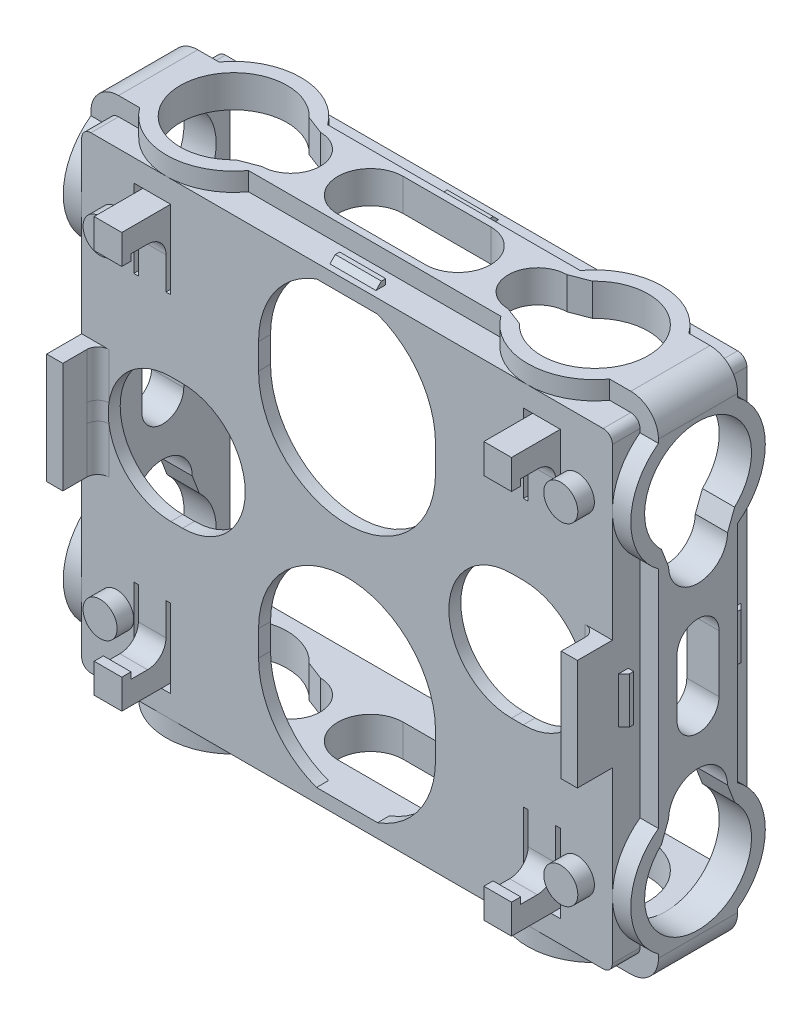
SolidWorks part; units mm, degrees
ref_plane "正面" through (0, 0, 0) normal (0, 0, 1) x (1, 0, 0)
ref_plane "平面" through (0, 0, 0) normal (0, 1, 0) x (1, 0, 0)
ref_plane "右側面" through (0, 0, 0) normal (1, 0, 0) x (0, 0, -1)
sketch "ｽｹｯﾁ2" plane through (0, 0, 0) normal (0, 0, 1) x (1, 0, 0)
  line L0 (0, 0) -> (54, 0) construction
  line L1 (0, 20) -> (54, 20) construction
  line L2 (-3.8, 47.4) -> (57.8, 47.4)
  line L3 (54, 0) -> (54, 40) construction
  line L4 (54, 40) -> (0, 40) construction
  line L5 (0, 40) -> (0, 0) construction
  line L6 (57.8, 47.4) -> (57.8, -7.4)
  line L7 (57.8, -7.4) -> (-3.8, -7.4)
  line L8 (-3.8, -7.4) -> (-3.8, 47.4)
  line L9 (27, 47.4) -> (27, -7.4) construction
  line L10 (27, 32.0981) -> (27, 34.8848) construction
  line L11 (17.3965, 32.0981) -> (17.3965, 34.8848)
  line L12 (36.6035, 32.0981) -> (36.6035, 34.8848)
  line L13 (27, 7.9019) -> (27, 5.1152) construction
  line L14 (17.3965, 7.9019) -> (17.3965, 5.1152)
  line L15 (36.6035, 7.9019) -> (36.6035, 5.1152)
  line L16 (52, 20) -> (27, 20) construction
  line L18 (46.1198, 20) -> (44.8536, 20) construction
  line L19 (52, 23.9649) -> (52, 16.0351) construction
  line L20 (46.1198, 13.1981) -> (44.8536, 13.1981)
  line L21 (46.1198, 26.8019) -> (44.8536, 26.8019)
  line L22 (7.8802, 20) -> (9.1464, 20) construction
  line L23 (7.8802, 13.1981) -> (9.1464, 13.1981)
  line L24 (7.8802, 26.8019) -> (9.1464, 26.8019)
  circle A0 centre (2, 2) radius 1.1 construction
  circle A1 centre (52, 2) radius 1.1 construction
  circle A2 centre (52, 38) radius 1.1 construction
  circle A3 centre (2, 38) radius 1.1 construction
  circle A4 centre (2, 38) radius 1.05
  circle A5 centre (2, 38) radius 1.8491
  circle A6 centre (2, 2) radius 1.8491
  circle A7 centre (52, 2) radius 1.8491
  circle A8 centre (52, 38) radius 1.8491
  circle A9 centre (52, 38) radius 1.05
  circle A10 centre (52, 2) radius 1.05
  circle A11 centre (2, 2) radius 1.05
  arc A12 (17.3965, 32.0981) -> (36.6035, 32.0981) centre (27, 32.0981) ccw
  arc A13 (36.6035, 34.8848) -> (17.3965, 34.8848) centre (27, 34.8848) ccw
  arc A14 (46.1198, 13.1981) -> (46.1198, 26.8019) centre (46.1198, 20) ccw
  arc A15 (44.8536, 26.8019) -> (44.8536, 13.1981) centre (44.8536, 20) ccw
  arc A16 (7.8802, 13.1981) -> (7.8802, 26.8019) centre (7.8802, 20) cw
  arc A17 (9.1464, 26.8019) -> (9.1464, 13.1981) centre (9.1464, 20) cw
  arc A18 (17.3965, 7.9019) -> (36.6035, 7.9019) centre (27, 7.9019) cw
  arc A19 (36.6035, 5.1152) -> (17.3965, 5.1152) centre (27, 5.1152) cw
  point P30 (27, 33.4915)
  point P41 (45.4867, 20)
  point P48 (8.5133, 20)
  point P55 (27, 6.5085)
  dimension "D3" = 2.2
  dimension "D8" = 2.1
  dimension "D9" = 30.8
  dimension "D1" = 40
  dimension "D2" = 54
  dimension "D4" = 27.4
  dimension "D5" = 27.4
extrude "ﾎﾞｽ - 押し出し1" add sketch "ｽｹｯﾁ2" along normal blind 1.5 contours L7 L8 L2 L6 | L15 A19 L14 A18 | L20 A15 L21 A14 | L11 A13 L12 A12 | A17 L23 A16 L24
extrude "ﾎﾞｽ - 押し出し3" add sketch "ｽｹｯﾁ2<4>" along normal blind 3.3 contours A7 | A6 | A5 | A8
sketch "ｽｹｯﾁ2<4>" plane through (0, 0, 0) normal (0, 0, 1) x (1, 0, 0) same geometry as "ｽｹｯﾁ2"
sketch "ｽｹｯﾁ6" plane through (-3.8, 0, 0) normal (-1, 0, 0) x (0, 0, 1)
  line L0 (1.5, -7.4) -> (0, -7.4) construction
  line L7 (1.5, -7.4) -> (1.5, 47.4) construction
  line L8 (-9.6, 33.9866) -> (-8.8, 31.9) construction
  line L9 (-5.8, 43.7) -> (-5.8, 19.9) construction
  line L12 (-13.1, 20) -> (0, 20) construction
  line L14 (-2.8, 31.9) -> (-2, 33.9866) construction
  line L15 (-9.6, 33.9866) -> (-8.8, 31.9) construction
  line L20 (-13.1, 47.4) -> (-13.1, -7.4)
  line L21 (1.5, -7.4) -> (1.5, 47.4)
  line L22 (-5.8, 23.1) -> (-5.8, 16.9) construction
  line L23 (-3.5215, 23.1) -> (-3.5215, 16.9)
  line L24 (-8.0785, 23.1) -> (-8.0785, 16.9)
  line L26 (1.5, 47.4) -> (-13.1, 47.4)
  line L27 (1.5, -7.4) -> (-13.1, -7.4)
  line L28 (-2.8, 31.9) -> (-2, 33.9866) construction
  line L29 (0, -7.4) -> (0, 47.4) construction
  line L30 (-2.8, 8.1) -> (-2, 6.0134) construction
  line L31 (-9.6, 6.0134) -> (-8.8, 8.1) construction
  line L32 (0, 16.9) -> (-11.6, 16.9) construction
  line L33 (-9.7702, 33.8718) -> (-8.9998, 31.8624)
  line L34 (-2.6002, 31.8624) -> (-1.8298, 33.8718)
  line L35 (-2.6002, 8.1376) -> (-1.8298, 6.1282)
  line L36 (-9.7702, 6.1282) -> (-8.9998, 8.1376)
  arc A3 (-2, 33.9866) -> (-9.6, 33.9866) centre (-5.8, 38.1) ccw construction
  arc A4 (-2, 33.9866) -> (-9.6, 33.9866) centre (-5.8, 38.1) ccw construction
  arc A10 (-8.8, 31.9) -> (-2.8, 31.9) centre (-5.8, 31.9) ccw construction
  arc A11 (-8.8, 31.9) -> (-2.8, 31.9) centre (-5.8, 31.9) ccw construction
  arc A12 (-3.5215, 23.1) -> (-8.0785, 23.1) centre (-5.8, 23.1) ccw
  arc A13 (-8.0785, 16.9) -> (-3.5215, 16.9) centre (-5.8, 16.9) ccw
  arc A14 (-8.8, 8.1) -> (-2.8, 8.1) centre (-5.8, 8.1) cw construction
  arc A15 (-2, 6.0134) -> (-9.6, 6.0134) centre (-5.8, 1.9) cw construction
  arc A16 (-1.8298, 33.8718) -> (-9.7702, 33.8718) centre (-5.8, 38.1) ccw
  arc A17 (-8.9998, 31.8624) -> (-2.6002, 31.8624) centre (-5.8, 31.9) ccw
  arc A18 (-8.9998, 8.1376) -> (-2.6002, 8.1376) centre (-5.8, 8.1) cw
  arc A19 (-1.8298, 6.1282) -> (-9.7702, 6.1282) centre (-5.8, 1.9) cw
  point P32 (-5.8, 20)
  dimension "D2" = 0.2
  dimension "D1" = 0
extrude "ﾎﾞｽ - 押し出し4" add sketch "ｽｹｯﾁ6" against normal up to surface (3.5 mm away)
sketch "ｽｹｯﾁ9" plane through (57.8, 0, 0) normal (1, 0, 0) x (0, 0, -1)
  line L2 (8.9998, 31.8624) -> (9.7702, 33.8718)
  line L3 (1.8298, 33.8718) -> (2.6002, 31.8624)
  line L4 (8.9998, 31.8624) -> (9.7702, 33.8718)
  line L5 (1.8298, 33.8718) -> (2.6002, 31.8624)
  line L6 (2.6002, 8.1376) -> (1.8298, 6.1282)
  line L7 (9.7702, 6.1282) -> (8.9998, 8.1376)
  line L8 (2.6002, 8.1376) -> (1.8298, 6.1282)
  line L9 (9.7702, 6.1282) -> (8.9998, 8.1376)
  line L10 (3.5215, 23.1) -> (3.5215, 16.9)
  line L11 (8.0785, 16.9) -> (8.0785, 23.1)
  line L12 (3.5215, 23.1) -> (3.5215, 16.9)
  line L13 (8.0785, 16.9) -> (8.0785, 23.1)
  line L16 (-1.5, 47.4) -> (-1.5, -7.4)
  line L17 (13.1, 47.4) -> (-1.5, 47.4)
  line L18 (13.1, -7.4) -> (13.1, 47.4)
  line L19 (-1.5, -7.4) -> (13.1, -7.4)
  line L20 (-1.5, 47.4) -> (-1.5, -7.4)
  line L21 (13.1, 47.4) -> (-1.5, 47.4)
  line L22 (13.1, -7.4) -> (13.1, 47.4)
  line L23 (-1.5, -7.4) -> (13.1, -7.4)
  arc A2 (2.6002, 31.8624) -> (8.9998, 31.8624) centre (5.8, 31.9) ccw
  arc A3 (9.7702, 33.8718) -> (1.8298, 33.8718) centre (5.8, 38.1) ccw
  arc A4 (2.6002, 31.8624) -> (8.9998, 31.8624) centre (5.8, 31.9) ccw
  arc A5 (9.7702, 33.8718) -> (1.8298, 33.8718) centre (5.8, 38.1) ccw
  arc A6 (1.8298, 6.1282) -> (9.7702, 6.1282) centre (5.8, 1.9) ccw
  arc A7 (8.9998, 8.1376) -> (2.6002, 8.1376) centre (5.8, 8.1) ccw
  arc A8 (1.8298, 6.1282) -> (9.7702, 6.1282) centre (5.8, 1.9) ccw
  arc A9 (8.9998, 8.1376) -> (2.6002, 8.1376) centre (5.8, 8.1) ccw
  arc A10 (3.5215, 16.9) -> (8.0785, 16.9) centre (5.8, 16.9) ccw
  arc A11 (8.0785, 23.1) -> (3.5215, 23.1) centre (5.8, 23.1) ccw
  arc A12 (3.5215, 16.9) -> (8.0785, 16.9) centre (5.8, 16.9) ccw
  arc A13 (8.0785, 23.1) -> (3.5215, 23.1) centre (5.8, 23.1) ccw
  dimension "D1" = 0
  dimension "D2" = 0
  dimension "D3" = 0
  dimension "D4" = 0
extrude "ﾎﾞｽ - 押し出し6" add sketch "ｽｹｯﾁ9" against normal up to surface (3.5 mm away)
sketch "ｽｹｯﾁ10" plane through (0, -7.4, 0) normal (0, -1, 0) x (1, 0, 0)
  line L0 (22.25, -5.8) -> (31.75, -5.8) construction
  line L1 (22.25, -2.25) -> (31.75, -2.25)
  line L2 (22.25, -9.35) -> (31.75, -9.35)
  line L5 (27, 1.5) -> (27, -13.1) construction
  line L10 (16.8, -5.8) -> (37.2, -5.8) construction
  line L11 (21.4, -5.8) -> (32.6, -5.8) construction
  line L13 (21.4, -2.55) -> (32.6, -2.55) construction
  line L14 (21.4, -9.05) -> (32.6, -9.05) construction
  line L17 (11.5134, -9.6) -> (13.6, -8.8)
  line L18 (57.8, 1.5) -> (57.8, -13.1) construction
  line L19 (57.8, 1.5) -> (-3.8, 1.5) construction
  line L20 (-3.8, 1.5) -> (-3.8, -13.1) construction
  line L22 (13.6, -2.8) -> (11.5134, -2)
  line L23 (57.8, 1.5) -> (57.8, -13.1)
  line L24 (57.8, 1.5) -> (-3.8, 1.5)
  line L25 (-3.8, 1.5) -> (-3.8, -13.1)
  line L27 (11.5134, -9.6) -> (13.6, -8.8) construction
  line L28 (13.6, -2.8) -> (11.5134, -2) construction
  line L29 (-3.8, -13.1) -> (57.8, -13.1)
  line L46 (11.6282, -9.7702) -> (13.6376, -8.9998)
  line L47 (13.6376, -2.6002) -> (11.6282, -1.8298)
  line L48 (40.4, -2.8) -> (42.4866, -2) construction
  line L49 (42.4866, -9.6) -> (40.4, -8.8) construction
  line L50 (40.3624, -2.6002) -> (42.3718, -1.8298)
  line L51 (42.3718, -9.7702) -> (40.3624, -8.9998)
  arc A1 (22.25, -2.25) -> (22.25, -9.35) centre (22.25, -5.8) ccw
  arc A2 (31.75, -9.35) -> (31.75, -2.25) centre (31.75, -5.8) ccw
  arc A8 (21.4, -2.55) -> (21.4, -9.05) centre (21.4, -5.8) ccw construction
  arc A9 (32.6, -9.05) -> (32.6, -2.55) centre (32.6, -5.8) ccw construction
  arc A12 (11.5134, -2) -> (11.5134, -9.6) centre (7.4, -5.8) ccw
  arc A13 (13.6, -8.8) -> (13.6, -2.8) centre (13.6, -5.8) ccw
  arc A14 (11.5134, -2) -> (11.5134, -9.6) centre (7.4, -5.8) ccw construction
  arc A15 (13.6, -8.8) -> (13.6, -2.8) centre (13.6, -5.8) ccw construction
  arc A32 (11.6282, -1.8298) -> (11.6282, -9.7702) centre (7.4, -5.8) ccw
  arc A33 (13.6376, -8.9998) -> (13.6376, -2.6002) centre (13.6, -5.8) ccw
  arc A34 (40.4, -8.8) -> (40.4, -2.8) centre (40.4, -5.8) cw construction
  arc A35 (42.4866, -2) -> (42.4866, -9.6) centre (46.6, -5.8) cw construction
  arc A36 (40.3624, -8.9998) -> (40.3624, -2.6002) centre (40.4, -5.8) cw
  arc A37 (42.3718, -1.8298) -> (42.3718, -9.7702) centre (46.6, -5.8) cw
  point P24 (27, -5.8)
  point P41 (27, -5.8)
  dimension "D1" = 0
  dimension "D4" = 11.2
  dimension "D2" = 0.2
  dimension "D3" = 6.5
extrude "ﾎﾞｽ - 押し出し7" add sketch "ｽｹｯﾁ10" against normal blind 3.5
sketch "ｽｹｯﾁ11" plane through (0, 47.4, 0) normal (0, 1, 0) x (1, 0, 0)
  line L2 (40.3624, 2.6002) -> (42.3718, 1.8298)
  line L3 (42.3718, 9.7702) -> (40.3624, 8.9998)
  line L4 (57.8, -1.5) -> (57.8, 13.1)
  line L5 (57.8, 13.1) -> (-3.8, 13.1)
  line L6 (-3.8, 13.1) -> (-3.8, -1.5)
  line L7 (-3.8, -1.5) -> (57.8, -1.5)
  line L8 (57.8, -1.5) -> (57.8, 13.1)
  line L9 (57.8, 13.1) -> (-3.8, 13.1)
  line L10 (-3.8, 13.1) -> (-3.8, -1.5)
  line L11 (-3.8, -1.5) -> (57.8, -1.5)
  line L12 (40.3624, 2.6002) -> (42.3718, 1.8298)
  line L13 (42.3718, 9.7702) -> (40.3624, 8.9998)
  line L14 (13.6376, 8.9998) -> (11.6282, 9.7702)
  line L15 (11.6282, 1.8298) -> (13.6376, 2.6002)
  line L16 (13.6376, 8.9998) -> (11.6282, 9.7702)
  line L17 (11.6282, 1.8298) -> (13.6376, 2.6002)
  line L18 (22.25, 2.25) -> (31.75, 2.25)
  line L19 (31.75, 9.35) -> (22.25, 9.35)
  line L20 (22.25, 2.25) -> (31.75, 2.25)
  line L21 (31.75, 9.35) -> (22.25, 9.35)
  arc A2 (42.3718, 1.8298) -> (42.3718, 9.7702) centre (46.6, 5.8) ccw
  arc A3 (40.3624, 8.9998) -> (40.3624, 2.6002) centre (40.4, 5.8) ccw
  arc A4 (42.3718, 1.8298) -> (42.3718, 9.7702) centre (46.6, 5.8) ccw
  arc A5 (40.3624, 8.9998) -> (40.3624, 2.6002) centre (40.4, 5.8) ccw
  arc A6 (13.6376, 2.6002) -> (13.6376, 8.9998) centre (13.6, 5.8) ccw
  arc A7 (11.6282, 9.7702) -> (11.6282, 1.8298) centre (7.4, 5.8) ccw
  arc A8 (13.6376, 2.6002) -> (13.6376, 8.9998) centre (13.6, 5.8) ccw
  arc A9 (11.6282, 9.7702) -> (11.6282, 1.8298) centre (7.4, 5.8) ccw
  arc A10 (31.75, 2.25) -> (31.75, 9.35) centre (31.75, 5.8) ccw
  arc A11 (22.25, 9.35) -> (22.25, 2.25) centre (22.25, 5.8) ccw
  arc A12 (31.75, 2.25) -> (31.75, 9.35) centre (31.75, 5.8) ccw
  arc A13 (22.25, 9.35) -> (22.25, 2.25) centre (22.25, 5.8) ccw
  dimension "D1" = 0
  dimension "D2" = 0
  dimension "D3" = 0
  dimension "D4" = 0
extrude "ﾎﾞｽ - 押し出し8" add sketch "ｽｹｯﾁ11" against normal blind 3.5
fillet "ﾌｨﾚｯﾄ1" radius 3 4 edges at (-3.8, -7.4, -5.8) (57.8, -7.4, -5.8) (57.8, 47.4, -5.8) (-3.8, 47.4, -5.8)
sketch "ｽｹｯﾁ12" plane through (0, 0, -13.1) normal (0, 0, -1) x (-1, 0, 0)
  line L1 (-55.8, 44.4) -> (-55.8, -4.4)
  line L2 (-54.8, -5.4) -> (0.8, -5.4)
  line L3 (1.8, -4.4) -> (1.8, 44.4)
  line L4 (-54.8, -7.4) -> (0.8, -7.4)
  line L5 (3.8, -4.4) -> (3.8, 44.4)
  line L6 (-54.8, -7.4) -> (0.8, -7.4)
  line L7 (-57.8, 44.4) -> (-57.8, -4.4)
  line L8 (0.8, 47.4) -> (-54.8, 47.4)
  line L9 (3.8, -4.4) -> (3.8, 44.4)
  line L10 (0.8, 47.4) -> (-54.8, 47.4)
  line L11 (-57.8, 44.4) -> (-57.8, -4.4)
  line L12 (0.8, 45.4) -> (-54.8, 45.4)
  line L16 (-57.8, 44.4) -> (-57.8, -4.4) construction
  line L17 (-54.8, -7.4) -> (0.8, -7.4) construction
  line L18 (0.8, 47.4) -> (-54.8, 47.4) construction
  arc A0 (-54.8, 45.4) -> (-55.8, 44.4) centre (-54.8, 44.4) ccw
  arc A1 (-55.8, -4.4) -> (-54.8, -5.4) centre (-54.8, -4.4) ccw
  arc A2 (0.8, -5.4) -> (1.8, -4.4) centre (0.8, -4.4) ccw
  arc A3 (1.8, 44.4) -> (0.8, 45.4) centre (0.8, 44.4) ccw
  arc A4 (0.8, -7.4) -> (3.8, -4.4) centre (0.8, -4.4) ccw
  arc A5 (3.8, 44.4) -> (0.8, 47.4) centre (0.8, 44.4) ccw
  arc A6 (-54.8, 47.4) -> (-57.8, 44.4) centre (-54.8, 44.4) ccw
  arc A7 (-57.8, -4.4) -> (-54.8, -7.4) centre (-54.8, -4.4) ccw
  arc A8 (0.8, -7.4) -> (3.8, -4.4) centre (0.8, -4.4) ccw
  arc A9 (3.8, 44.4) -> (0.8, 47.4) centre (0.8, 44.4) ccw
  arc A10 (-54.8, 47.4) -> (-57.8, 44.4) centre (-54.8, 44.4) ccw
  arc A11 (-57.8, -4.4) -> (-54.8, -7.4) centre (-54.8, -4.4) ccw
  dimension "D1" = 0
  dimension "D2" = 2
extrude "ｶｯﾄ - 押し出し1" cut sketch "ｽｹｯﾁ12" against normal blind 3
sketch "ｽｹｯﾁ22" plane through (0, 0, 1.5) normal (0, 0, 1) x (1, 0, 0)
  line L0 (-1.8, 44.4) -> (-1.8, -4.4)
  line L1 (-0.8, -5.4) -> (54.8, -5.4)
  line L2 (55.8, -4.4) -> (55.8, 44.4)
  line L3 (54.8, 45.4) -> (-0.8, 45.4)
  line L4 (-3.8, 44.4) -> (-3.8, -4.4)
  line L5 (-0.8, -7.4) -> (54.8, -7.4)
  line L6 (57.8, -4.4) -> (57.8, 44.4)
  line L7 (54.8, 47.4) -> (-0.8, 47.4)
  line L8 (-3.8, 44.4) -> (-3.8, -4.4)
  line L9 (-0.8, -7.4) -> (54.8, -7.4)
  line L10 (57.8, -4.4) -> (57.8, 44.4)
  line L11 (54.8, 47.4) -> (-0.8, 47.4)
  arc A0 (-1.8, -4.4) -> (-0.8, -5.4) centre (-0.8, -4.4) ccw
  arc A1 (54.8, -5.4) -> (55.8, -4.4) centre (54.8, -4.4) ccw
  arc A2 (55.8, 44.4) -> (54.8, 45.4) centre (54.8, 44.4) ccw
  arc A3 (-0.8, 45.4) -> (-1.8, 44.4) centre (-0.8, 44.4) ccw
  arc A4 (-3.8, -4.4) -> (-0.8, -7.4) centre (-0.8, -4.4) ccw
  arc A5 (54.8, -7.4) -> (57.8, -4.4) centre (54.8, -4.4) ccw
  arc A6 (57.8, 44.4) -> (54.8, 47.4) centre (54.8, 44.4) ccw
  arc A7 (-0.8, 47.4) -> (-3.8, 44.4) centre (-0.8, 44.4) ccw
  arc A8 (-3.8, -4.4) -> (-0.8, -7.4) centre (-0.8, -4.4) ccw
  arc A9 (54.8, -7.4) -> (57.8, -4.4) centre (54.8, -4.4) ccw
  arc A10 (57.8, 44.4) -> (54.8, 47.4) centre (54.8, 44.4) ccw
  arc A11 (-0.8, 47.4) -> (-3.8, 44.4) centre (-0.8, 44.4) ccw
  dimension "D1" = 0
  dimension "D2" = 2
extrude "ｶｯﾄ - 押し出し2" cut sketch "ｽｹｯﾁ22" against normal blind 3
sketch "ｽｹｯﾁ21" plane through (0, -7.4, 0) normal (0, -1, 0) x (1, 0, 0)
  line L0 (-0.8, -5.8) -> (-7.911, -5.8) construction
  line L1 (11.2923, -1.5) -> (42.7077, -1.5) construction
  line L5 (1.5008, -10.1) -> (3.5077, -10.1)
  line L6 (-0.8, -1.5) -> (3.5077, -1.5) construction
  line L10 (11.2923, -1.5) -> (13.2992, -1.5)
  line L11 (-0.8, -1.5) -> (-0.8, -10.1) construction
  line L12 (1.5008, -1.5) -> (3.5077, -1.5)
  line L19 (11.2923, -10.1) -> (13.2992, -10.1)
  line L23 (27, 1.5) -> (27, 9.2892) construction
  line L24 (-0.8, 1.5) -> (54.8, 1.5) construction
  line L25 (42.7077, -10.1) -> (40.7008, -10.1)
  line L26 (52.4992, -1.5) -> (50.4923, -1.5)
  line L27 (42.7077, -1.5) -> (40.7008, -1.5)
  line L28 (52.4992, -10.1) -> (50.4923, -10.1)
  arc A6 (13.2992, -10.1) -> (1.5008, -10.1) centre (7.4, -5.8) cw
  arc A10 (11.2923, -1.5) -> (3.5077, -1.5) centre (7.4, -5.8) ccw construction
  arc A13 (11.2923, -1.5) -> (3.5077, -1.5) centre (7.4, -5.8) ccw
  arc A14 (13.2992, -1.5) -> (1.5008, -1.5) centre (7.4, -5.8) ccw
  arc A25 (12.2989, -0.3879) -> (2.5011, -0.3879) centre (7.4, -5.8) ccw construction
  arc A26 (11.2923, -10.1) -> (3.5077, -10.1) centre (7.4, -5.8) cw
  arc A27 (42.7077, -10.1) -> (50.4923, -10.1) centre (46.6, -5.8) ccw
  arc A28 (40.7008, -1.5) -> (52.4992, -1.5) centre (46.6, -5.8) cw
  arc A29 (42.7077, -1.5) -> (50.4923, -1.5) centre (46.6, -5.8) cw
  arc A30 (40.7008, -10.1) -> (52.4992, -10.1) centre (46.6, -5.8) ccw
  dimension "D1" = 1.5
extrude "ﾎﾞｽ - 押し出し9" add sketch "ｽｹｯﾁ21" against normal up to surface (2 mm away) up to face at (27, -5.4, -0.375)
sketch "ｽｹｯﾁ23" plane through (0, 47.4, 0) normal (0, 1, 0) x (1, 0, 0)
  line L2 (1.5008, 10.1) -> (3.5077, 10.1)
  line L3 (11.2923, 10.1) -> (13.2992, 10.1)
  line L4 (1.5008, 10.1) -> (3.5077, 10.1)
  line L5 (11.2923, 10.1) -> (13.2992, 10.1)
  line L6 (52.4992, 1.5) -> (50.4923, 1.5)
  line L7 (42.7077, 1.5) -> (40.7008, 1.5)
  line L8 (52.4992, 1.5) -> (50.4923, 1.5)
  line L9 (42.7077, 1.5) -> (40.7008, 1.5)
  line L10 (40.7008, 10.1) -> (42.7077, 10.1)
  line L11 (50.4923, 10.1) -> (52.4992, 10.1)
  line L12 (40.7008, 10.1) -> (42.7077, 10.1)
  line L13 (50.4923, 10.1) -> (52.4992, 10.1)
  line L14 (13.2992, 1.5) -> (11.2923, 1.5)
  line L15 (3.5077, 1.5) -> (1.5008, 1.5)
  line L16 (13.2992, 1.5) -> (11.2923, 1.5)
  line L17 (3.5077, 1.5) -> (1.5008, 1.5)
  arc A2 (11.2923, 10.1) -> (3.5077, 10.1) centre (7.4, 5.8) ccw
  arc A3 (13.2992, 10.1) -> (1.5008, 10.1) centre (7.4, 5.8) ccw
  arc A4 (11.2923, 10.1) -> (3.5077, 10.1) centre (7.4, 5.8) ccw
  arc A5 (13.2992, 10.1) -> (1.5008, 10.1) centre (7.4, 5.8) ccw
  arc A6 (42.7077, 1.5) -> (50.4923, 1.5) centre (46.6, 5.8) ccw
  arc A7 (40.7008, 1.5) -> (52.4992, 1.5) centre (46.6, 5.8) ccw
  arc A8 (42.7077, 1.5) -> (50.4923, 1.5) centre (46.6, 5.8) ccw
  arc A9 (40.7008, 1.5) -> (52.4992, 1.5) centre (46.6, 5.8) ccw
  arc A10 (52.4992, 10.1) -> (40.7008, 10.1) centre (46.6, 5.8) ccw
  arc A11 (50.4923, 10.1) -> (42.7077, 10.1) centre (46.6, 5.8) ccw
  arc A12 (52.4992, 10.1) -> (40.7008, 10.1) centre (46.6, 5.8) ccw
  arc A13 (50.4923, 10.1) -> (42.7077, 10.1) centre (46.6, 5.8) ccw
  arc A14 (1.5008, 1.5) -> (13.2992, 1.5) centre (7.4, 5.8) ccw
  arc A15 (3.5077, 1.5) -> (11.2923, 1.5) centre (7.4, 5.8) ccw
  arc A16 (1.5008, 1.5) -> (13.2992, 1.5) centre (7.4, 5.8) ccw
  arc A17 (3.5077, 1.5) -> (11.2923, 1.5) centre (7.4, 5.8) ccw
  dimension "D1" = 0
  dimension "D2" = 0
  dimension "D3" = 0
  dimension "D4" = 0
extrude "ﾎﾞｽ - 押し出し10" add sketch "ｽｹｯﾁ23" against normal up to surface (2 mm away) up to face at (27, 45.4, -11.225)
sketch "ｽｹｯﾁ24" plane through (57.8, 0, 0) normal (1, 0, 0) x (0, 0, -1)
  line L0 (1.5, 5.7923) -> (1.5, 34.2077) construction
  line L1 (1.5, 41.9923) -> (1.5, 44.4) construction
  line L3 (1.5, 41.9923) -> (1.5, 43.9992)
  line L4 (1.5, 32.2008) -> (1.5, 34.2077)
  line L7 (5.8, 44.4) -> (5.8, 52.6929) construction
  line L8 (10.1, 44.4) -> (1.5, 44.4) construction
  line L9 (10.1, 32.2008) -> (10.1, 34.2077)
  line L10 (10.1, 41.9923) -> (10.1, 43.9992)
  line L11 (-1.5, 20) -> (-9.7166, 20) construction
  line L15 (-1.5, -4.4) -> (-1.5, 44.4) construction
  line L22 (10.1, -1.9923) -> (10.1, -3.9992)
  line L23 (10.1, 7.7992) -> (10.1, 5.7923)
  line L24 (1.5, 7.7992) -> (1.5, 5.7923)
  line L25 (1.5, -1.9923) -> (1.5, -3.9992)
  arc A0 (1.5, 43.9992) -> (1.5, 32.2008) centre (5.8, 38.1) ccw
  arc A1 (0.3879, 42.9989) -> (0.3879, 33.2011) centre (5.8, 38.1) ccw construction
  arc A7 (1.5, 41.9923) -> (1.5, 34.2077) centre (5.8, 38.1) ccw construction
  arc A11 (1.5, 41.9923) -> (1.5, 34.2077) centre (5.8, 38.1) ccw
  arc A12 (10.1, 43.9992) -> (10.1, 32.2008) centre (5.8, 38.1) cw
  arc A13 (10.1, -3.9992) -> (10.1, 7.7992) centre (5.8, 1.9) ccw
  arc A14 (1.5, -1.9923) -> (1.5, 5.7923) centre (5.8, 1.9) cw
  arc A15 (1.5, -3.9992) -> (1.5, 7.7992) centre (5.8, 1.9) cw
  arc A16 (10.1, 34.2077) -> (10.1, 41.9923) centre (5.8, 38.1) ccw construction
  arc A17 (10.1, -1.9923) -> (10.1, 5.7923) centre (5.8, 1.9) ccw construction
  arc A18 (10.1, 34.2077) -> (10.1, 41.9923) centre (5.8, 38.1) ccw
  arc A19 (10.1, -1.9923) -> (10.1, 5.7923) centre (5.8, 1.9) ccw
  dimension "D1" = 1.5
extrude "ﾎﾞｽ - 押し出し11" add sketch "ｽｹｯﾁ24" against normal up to surface (2 mm away) up to face at (55.8, 20, -0.375)
sketch "ｽｹｯﾁ25" plane through (-3.8, 0, 0) normal (-1, 0, 0) x (0, 0, 1)
  line L2 (-1.5, 43.9992) -> (-1.5, 41.9923)
  line L3 (-1.5, 34.2077) -> (-1.5, 32.2008)
  line L4 (-1.5, 43.9992) -> (-1.5, 41.9923)
  line L5 (-1.5, 34.2077) -> (-1.5, 32.2008)
  line L6 (-1.5, 7.7992) -> (-1.5, 5.7923)
  line L7 (-1.5, -1.9923) -> (-1.5, -3.9992)
  line L8 (-1.5, 7.7992) -> (-1.5, 5.7923)
  line L9 (-1.5, -1.9923) -> (-1.5, -3.9992)
  line L10 (-10.1, -3.9992) -> (-10.1, -1.9923)
  line L11 (-10.1, 5.7923) -> (-10.1, 7.7992)
  line L12 (-10.1, -3.9992) -> (-10.1, -1.9923)
  line L13 (-10.1, 5.7923) -> (-10.1, 7.7992)
  line L14 (-10.1, 32.2008) -> (-10.1, 34.2077)
  line L15 (-10.1, 41.9923) -> (-10.1, 43.9992)
  line L16 (-10.1, 32.2008) -> (-10.1, 34.2077)
  line L17 (-10.1, 41.9923) -> (-10.1, 43.9992)
  arc A2 (-1.5, 32.2008) -> (-1.5, 43.9992) centre (-5.8, 38.1) ccw
  arc A3 (-1.5, 34.2077) -> (-1.5, 41.9923) centre (-5.8, 38.1) ccw
  arc A4 (-1.5, 32.2008) -> (-1.5, 43.9992) centre (-5.8, 38.1) ccw
  arc A5 (-1.5, 34.2077) -> (-1.5, 41.9923) centre (-5.8, 38.1) ccw
  arc A6 (-1.5, -1.9923) -> (-1.5, 5.7923) centre (-5.8, 1.9) ccw
  arc A7 (-1.5, -3.9992) -> (-1.5, 7.7992) centre (-5.8, 1.9) ccw
  arc A8 (-1.5, -1.9923) -> (-1.5, 5.7923) centre (-5.8, 1.9) ccw
  arc A9 (-1.5, -3.9992) -> (-1.5, 7.7992) centre (-5.8, 1.9) ccw
  arc A10 (-10.1, 7.7992) -> (-10.1, -3.9992) centre (-5.8, 1.9) ccw
  arc A11 (-10.1, 5.7923) -> (-10.1, -1.9923) centre (-5.8, 1.9) ccw
  arc A12 (-10.1, 7.7992) -> (-10.1, -3.9992) centre (-5.8, 1.9) ccw
  arc A13 (-10.1, 5.7923) -> (-10.1, -1.9923) centre (-5.8, 1.9) ccw
  arc A14 (-10.1, 43.9992) -> (-10.1, 32.2008) centre (-5.8, 38.1) ccw
  arc A15 (-10.1, 41.9923) -> (-10.1, 34.2077) centre (-5.8, 38.1) ccw
  arc A16 (-10.1, 43.9992) -> (-10.1, 32.2008) centre (-5.8, 38.1) ccw
  arc A17 (-10.1, 41.9923) -> (-10.1, 34.2077) centre (-5.8, 38.1) ccw
  dimension "D1" = 0
  dimension "D2" = 0
  dimension "D3" = 0
  dimension "D4" = 0
extrude "ﾎﾞｽ - 押し出し12" add sketch "ｽｹｯﾁ25" against normal up to surface (2 mm away) up to face at (-1.8, 20, -11.225)
ref_plane "平面1" through (0, 20, 0) normal (0, 1, 0) x (1, 0, 0)
sketch "ｽｹｯﾁ26" plane through (0, 20, 0) normal (0, 1, 0) x (1, 0, 0)
  line L1 (-1.8, 13.1) -> (55.8, 13.1) construction
  line L2 (56.3887, -0.2466) -> (56.3887, 0.2234)
  line L3 (55.8, -0.8353) -> (56.3887, -0.2466)
  line L4 (55.8, 0.2234) -> (55.8, -0.8353)
  line L5 (27, 13.1) -> (27, 21.7666) construction
  line L6 (55.8, 0.2234) -> (56.3887, 0.2234)
  line L7 (57.8, 5.8) -> (54.8, 5.8) construction
  line L8 (57.8, 10.1) -> (57.8, 1.5) construction
  line L9 (54.8, 1.5) -> (54.8, 10.1) construction
  line L10 (55.8, 11.3766) -> (56.3887, 11.3766)
  line L11 (55.8, 11.3766) -> (55.8, 12.4353)
  line L12 (55.8, 12.4353) -> (56.3887, 11.8466)
  line L13 (56.3887, 11.8466) -> (56.3887, 11.3766)
  line L14 (-2.3887, 11.8466) -> (-2.3887, 11.3766)
  line L15 (-1.8, 12.4353) -> (-2.3887, 11.8466)
  line L16 (-1.8, 11.3766) -> (-1.8, 12.4353)
  line L17 (-1.8, 11.3766) -> (-2.3887, 11.3766)
  line L18 (-1.8, 0.2234) -> (-2.3887, 0.2234)
  line L19 (-1.8, 0.2234) -> (-1.8, -0.8353)
  line L20 (-1.8, -0.8353) -> (-2.3887, -0.2466)
  line L21 (-2.3887, -0.2466) -> (-2.3887, 0.2234)
extrude "ﾎﾞｽ - 押し出し13" add sketch "ｽｹｯﾁ26" along normal mid plane 5
ref_plane "平面3" through (27, 0, 0) normal (-1, 0, 0) x (0, 0, 1)
sketch "ｽｹｯﾁ27" plane through (27, 0, 0) normal (-1, 0, 0) x (0, 0, 1)
  line L0 (0.2713, 45.9887) -> (-0.1987, 45.9887)
  line L1 (0.86, 45.4) -> (0.2713, 45.9887)
  line L2 (-0.1987, 45.4) -> (0.86, 45.4)
  line L3 (-1.5, -5.4) -> (1.5, -5.4) construction
  line L4 (-5.8, 47.4) -> (-5.8, 44.4) construction
  line L5 (-1.5, 45.4) -> (1.5, 45.4) construction
  line L6 (-1.5, -5.4) -> (1.5, -5.4) construction
  line L7 (1.5, 45.4) -> (1.5, -5.4) construction
  line L8 (1.5, 20) -> (10.2973, 20) construction
  line L9 (-0.1987, 45.9887) -> (-0.1987, 45.4)
  line L10 (-1.5, 47.4) -> (-10.1, 47.4) construction
  line L11 (-10.1, 44.4) -> (-1.5, 44.4) construction
  line L12 (-11.4013, 45.4) -> (-12.46, 45.4)
  line L13 (-12.46, 45.4) -> (-11.8713, 45.9887)
  line L14 (-11.8713, 45.9887) -> (-11.4013, 45.9887)
  line L15 (-11.4013, 45.4) -> (-11.4013, 45.9887)
  line L16 (-11.4013, -5.4) -> (-11.4013, -5.9887)
  line L17 (-11.8713, -5.9887) -> (-11.4013, -5.9887)
  line L18 (-12.46, -5.4) -> (-11.8713, -5.9887)
  line L19 (-11.4013, -5.4) -> (-12.46, -5.4)
  line L20 (-0.1987, -5.9887) -> (-0.1987, -5.4)
  line L21 (-0.1987, -5.4) -> (0.86, -5.4)
  line L22 (0.86, -5.4) -> (0.2713, -5.9887)
  line L23 (0.2713, -5.9887) -> (-0.1987, -5.9887)
extrude "ﾎﾞｽ - 押し出し14" add sketch "ｽｹｯﾁ27" along normal mid plane 5
ref_plane "平面4" through (0, 0, 2.9) normal (0, 0, 1) x (1, 0, 0)
sketch "ｽｹｯﾁ28" plane through (0, 0, 1.5) normal (0, 0, 1) x (1, 0, 0)
  line L0 (0, 0) -> (54, 0) construction
  line L1 (27, 20) -> (-13.2669, 20) construction
  line L2 (-0.05, 14) -> (-1.8, 14)
  line L3 (54, 0) -> (54, 40) construction
  line L4 (54, 40) -> (0, 40) construction
  line L5 (0, 40) -> (0, 0) construction
  line L6 (-1.8, 38.1) -> (-1.8, 1.9) construction
  line L7 (-1.8, 14) -> (-1.8, 26)
  line L8 (-0.05, 26) -> (-0.05, 14)
  line L9 (27, 47.4) -> (27, -7.4) construction
  line L10 (55.8, 26) -> (54.05, 26)
  line L11 (54.05, 26) -> (54.05, 14)
  line L12 (55.8, 14) -> (55.8, 26)
  line L13 (54.05, 14) -> (55.8, 14)
  line L14 (4.35, 42.5) -> (4.35, 40)
  line L15 (4.35, 42.5) -> (7.35, 42.5)
  line L16 (7.35, 42.5) -> (7.35, 40)
  line L17 (4.35, 40) -> (7.35, 40)
  line L18 (4.35, 0) -> (7.35, 0)
  line L19 (7.35, -2.5) -> (7.35, 0)
  line L20 (4.35, -2.5) -> (7.35, -2.5)
  line L21 (4.35, -2.5) -> (4.35, 0)
  line L22 (49.65, -2.5) -> (49.65, 0)
  line L23 (49.65, -2.5) -> (46.65, -2.5)
  line L24 (46.65, -2.5) -> (46.65, 0)
  line L25 (49.65, 0) -> (46.65, 0)
  line L26 (49.65, 40) -> (46.65, 40)
  line L27 (46.65, 42.5) -> (46.65, 40)
  line L28 (49.65, 42.5) -> (46.65, 42.5)
  line L29 (49.65, 42.5) -> (49.65, 40)
  line L30 (-1.8, 26) -> (-0.05, 26)
  circle A21 centre (2, 38) radius 1.8491
  circle A22 centre (2, 38) radius 1.8491 construction
  dimension "D7" = 3
  dimension "D2" = 0.1
  dimension "D6" = 2.35
  dimension "D8" = 2.5
  dimension "D1" = 0
extrude "ﾎﾞｽ - 押し出し15" add sketch "ｽｹｯﾁ28" along normal blind 3.8
sketch "ｽｹｯﾁ29" plane through (0, 0, 5.3) normal (0, 0, 1) x (1, 0, 0)
  line L0 (4.35, 39.3) -> (7.35, 39.3)
  line L1 (7.35, 42.5) -> (7.35, 39.3)
  line L2 (4.35, 42.5) -> (4.35, 39.3)
  line L3 (7.35, 42.5) -> (4.35, 42.5) construction
  line L4 (7.35, 42.5) -> (4.35, 42.5)
  line L5 (-3.8, 20) -> (-15.3419, 20) construction
  line L6 (-3.8, 32.2008) -> (-3.8, 7.7992) construction
  line L7 (7.35, -2.5) -> (4.35, -2.5)
  line L8 (4.35, -2.5) -> (4.35, 0.7)
  line L9 (7.35, -2.5) -> (7.35, 0.7)
  line L11 (4.35, 0.7) -> (7.35, 0.7)
  line L12 (27, 45.4) -> (27, 55.9669) construction
  line L13 (46.6, 45.4) -> (7.4, 45.4) construction
  line L14 (49.65, 0.7) -> (46.65, 0.7)
  line L16 (46.65, -2.5) -> (46.65, 0.7)
  line L17 (49.65, -2.5) -> (49.65, 0.7)
  line L18 (46.65, -2.5) -> (49.65, -2.5)
  line L19 (46.65, 42.5) -> (49.65, 42.5)
  line L20 (49.65, 42.5) -> (49.65, 39.3)
  line L21 (46.65, 42.5) -> (46.65, 39.3)
  line L22 (49.65, 39.3) -> (46.65, 39.3)
extrude "ﾎﾞｽ - 押し出し16" add sketch "ｽｹｯﾁ29" along normal blind 1
sketch "ｽｹｯﾁ30" plane through (0, 0, 1.5) normal (0, 0, 1) x (1, 0, 0)
  line L0 (4.35, 42.5) -> (4.35, 34.5)
  line L1 (7.35, 42.5) -> (7.35, 34.5)
  line L2 (7.85, 43) -> (7.85, 34.5)
  line L3 (7.85, 43) -> (3.85, 43)
  line L4 (7.35, 42.5) -> (4.35, 42.5)
  line L5 (4.35, 42.5) -> (4.35, 39.3)
  line L6 (4.35, 39.3) -> (7.35, 39.3)
  line L7 (7.35, 39.3) -> (7.35, 42.5)
  line L8 (7.35, 42.5) -> (4.35, 42.5)
  line L9 (3.85, 43) -> (3.85, 34.5)
  line L10 (3.85, 34.5) -> (4.35, 34.5)
  line L11 (7.35, 34.5) -> (7.85, 34.5)
  line L12 (-3.8, 20) -> (-12.0524, 20) construction
  line L14 (-3.8, 32.2008) -> (-3.8, 7.7992) construction
  line L15 (7.35, 5.5) -> (7.85, 5.5)
  line L16 (3.85, 5.5) -> (4.35, 5.5)
  line L17 (3.85, -3) -> (3.85, 5.5)
  line L18 (7.35, -2.5) -> (4.35, -2.5)
  line L19 (7.85, -3) -> (3.85, -3)
  line L20 (7.85, -3) -> (7.85, 5.5)
  line L21 (7.35, -2.5) -> (7.35, 5.5)
  line L22 (4.35, -2.5) -> (4.35, 5.5)
  line L24 (27, 47.4) -> (27, 61.077) construction
  line L25 (40.7008, 47.4) -> (13.2992, 47.4) construction
  line L26 (49.65, -2.5) -> (49.65, 5.5)
  line L27 (46.65, -2.5) -> (46.65, 5.5)
  line L28 (46.15, -3) -> (46.15, 5.5)
  line L29 (46.15, -3) -> (50.15, -3)
  line L30 (46.65, -2.5) -> (49.65, -2.5)
  line L31 (50.15, -3) -> (50.15, 5.5)
  line L32 (50.15, 5.5) -> (49.65, 5.5)
  line L33 (46.65, 5.5) -> (46.15, 5.5)
  line L34 (46.65, 34.5) -> (46.15, 34.5)
  line L35 (50.15, 34.5) -> (49.65, 34.5)
  line L36 (50.15, 43) -> (50.15, 34.5)
  line L37 (46.65, 42.5) -> (49.65, 42.5)
  line L38 (46.15, 43) -> (50.15, 43)
  line L39 (46.15, 43) -> (46.15, 34.5)
  line L40 (46.65, 42.5) -> (46.65, 34.5)
  line L41 (49.65, 42.5) -> (49.65, 34.5)
  dimension "D2" = 8
  dimension "D3" = 0.5
  dimension "D1" = 0
extrude "ｶｯﾄ - 押し出し4" cut sketch "ｽｹｯﾁ30" against normal up to vertex up to point (3.55, -3.9, 0)
sketch "ｽｹｯﾁ31" plane through (0, 0, 0) normal (0, 0, -1) x (-1, 0, 0)
  line L4 (0.3, -3.9) -> (0.3, 1.9)
  line L5 (0.3, 43.9) -> (-7.4, 43.9)
  line L6 (-54.3, 1.9) -> (-54.3, -3.9)
  line L7 (-54.3, -3.9) -> (-46.6, -3.9)
  line L8 (0.3, -3.9) -> (0.3, 1.9)
  line L9 (0.3, 43.9) -> (-7.4, 43.9)
  line L10 (-54.3, 1.9) -> (-54.3, -3.9)
  line L11 (-54.3, -3.9) -> (-46.6, -3.9)
  line L18 (-17.3965, 34.8848) -> (-17.3965, 32.0981)
  line L19 (-17.3965, 34.8848) -> (-17.3965, 32.0981)
  line L20 (-36.6035, 32.0981) -> (-36.6035, 34.8848)
  line L21 (-36.6035, 32.0981) -> (-36.6035, 34.8848)
  line L22 (-7.4, 43.9) -> (-23.6902, 43.9)
  line L23 (-7.4, 43.9) -> (-23.6902, 43.9)
  line L24 (-36.6035, 5.1152) -> (-36.6035, 7.9019)
  line L25 (-36.6035, 5.1152) -> (-36.6035, 7.9019)
  line L26 (-17.3965, 7.9019) -> (-17.3965, 5.1152)
  line L27 (-17.3965, 7.9019) -> (-17.3965, 5.1152)
  line L28 (-7.4, -3.9) -> (0.3, -3.9)
  line L29 (-7.4, -3.9) -> (0.3, -3.9)
  line L32 (0.3, 38.1) -> (0.3, 43.9)
  line L33 (0.3, 38.1) -> (0.3, 43.9)
  line L34 (0.3, 1.9) -> (0.3, 38.1)
  line L35 (0.3, 1.9) -> (0.3, 38.1)
  line L38 (-54.3, 38.1) -> (-54.3, 1.9)
  line L39 (-54.3, 38.1) -> (-54.3, 1.9)
  line L40 (-30.3098, 43.9) -> (-46.6, 43.9)
  line L41 (-30.3098, 43.9) -> (-46.6, 43.9)
  line L43 (-23.6902, -3.9) -> (-7.4, -3.9)
  line L44 (-23.6902, -3.9) -> (-7.4, -3.9)
  line L46 (-46.6, -3.9) -> (-30.3098, -3.9)
  line L47 (-46.6, -3.9) -> (-30.3098, -3.9)
  line L50 (-46.6, 43.9) -> (-54.3, 43.9)
  line L51 (-46.6, 43.9) -> (-54.3, 43.9)
  line L52 (-54.3, 43.9) -> (-54.3, 38.1)
  line L53 (-54.3, 43.9) -> (-54.3, 38.1)
  arc A6 (-17.3965, 34.8848) -> (-23.6902, 43.9) centre (-27, 34.8848) ccw
  arc A7 (-17.3965, 34.8848) -> (-23.6902, 43.9) centre (-27, 34.8848) ccw
  arc A8 (-36.6035, 32.0981) -> (-17.3965, 32.0981) centre (-27, 32.0981) ccw
  arc A9 (-36.6035, 32.0981) -> (-17.3965, 32.0981) centre (-27, 32.0981) ccw
  arc A10 (-30.3098, 43.9) -> (-36.6035, 34.8848) centre (-27, 34.8848) ccw
  arc A11 (-30.3098, 43.9) -> (-36.6035, 34.8848) centre (-27, 34.8848) ccw
  arc A12 (-36.6035, 5.1152) -> (-30.3098, -3.9) centre (-27, 5.1152) ccw
  arc A13 (-36.6035, 5.1152) -> (-30.3098, -3.9) centre (-27, 5.1152) ccw
  arc A14 (-17.3965, 7.9019) -> (-36.6035, 7.9019) centre (-27, 7.9019) ccw
  arc A15 (-17.3965, 7.9019) -> (-36.6035, 7.9019) centre (-27, 7.9019) ccw
  arc A16 (-23.6902, -3.9) -> (-17.3965, 5.1152) centre (-27, 5.1152) ccw
  arc A17 (-23.6902, -3.9) -> (-17.3965, 5.1152) centre (-27, 5.1152) ccw
  dimension "D1" = 0
extrude "ｶｯﾄ - 押し出し5" cut sketch "ｽｹｯﾁ31" against normal blind 0.2
fillet "ﾌｨﾚｯﾄ2" radius 2 4 edges at (48.15, 40, 1.5) (48.15, 0, 1.5) (5.85, 0, 1.5) (5.85, 40, 1.5)
fillet "ﾌｨﾚｯﾄ3" radius 1.2 2 edges at (-0.05, 20, 1.5) (54.05, 20, 1.5)
fillet "ﾌｨﾚｯﾄ4" [suppressed] radius 2
